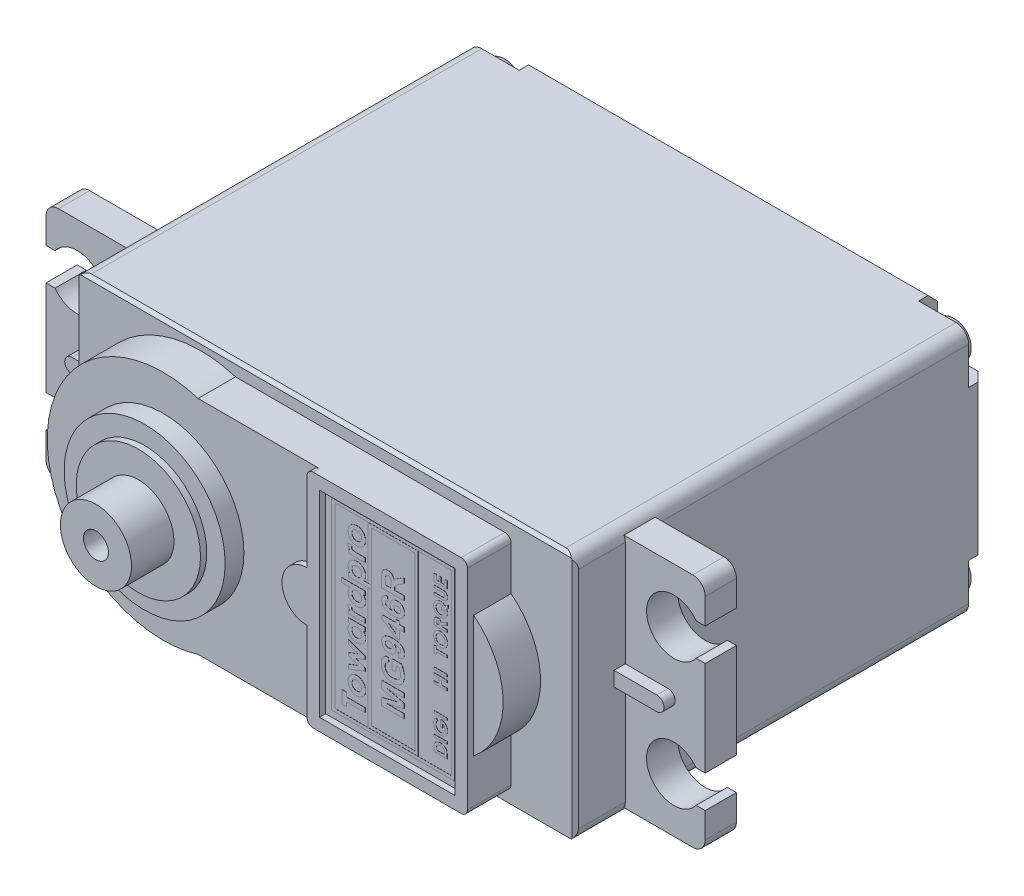
SolidWorks part; units mm, degrees
ref_plane "Front Plane" through (0, 0, 0) normal (0, 0, 1) x (1, 0, 0)
ref_plane "Top Plane" through (0, 0, 0) normal (0, 1, 0) x (1, 0, 0)
ref_plane "Right Plane" through (0, 0, 0) normal (1, 0, 0) x (0, 0, -1)
ref_plane "Plane1" through (0, -10, 0) normal (0, -1, 0) x (1, 0, 0)
sketch "Sketch1" plane through (0, -10, 0) normal (0, -1, 0) x (1, 0, 0)
  line L0 (-20, 16.5) -> (-20, -16.5)
  line L1 (-20, -16.5) -> (20, -16.5)
  line L2 (20, -16.5) -> (20, 16.5)
  line L3 (20, 16.5) -> (-20, 16.5)
extrude "Boss-Extrude1" add sketch "Sketch1" against normal blind 20
sketch "Sketch2" plane through (0, 0, 16.5) normal (0, 0, 1) x (1, 0, 0)
  line L0 (14.8541, 8.875) -> (14.8541, -8.875)
  line L1 (14.8541, -8.875) -> (-7.2207, -8.875)
  line L2 (-7.2207, 8.875) -> (14.8541, 8.875)
  arc A0 (-7.2207, -8.875) -> (-7.2207, 8.875) centre (-10, 0) cw
extrude "Boss-Extrude2" add sketch "Sketch2" along normal blind 3
sketch "Sketch3" plane through (0, 0, 19.5) normal (0, 0, 1) x (1, 0, 0)
  line L0 (2.0041, 8.875) -> (14.8541, 8.875)
  line L1 (14.8541, 8.875) -> (14.8541, -8.875)
  line L2 (14.8541, -8.875) -> (2.0041, -8.875)
  line L3 (2.0041, -8.875) -> (2.0041, 8.875)
extrude "Boss-Extrude3" add sketch "Sketch3" along normal blind 0.5
sketch "Sketch4" plane through (0, 0, 19.5) normal (0, 0, 1) x (1, 0, 0)
  line L0 (2.0041, 2) -> (2.0041, -2)
  arc A0 (2.0041, -2) -> (2.0041, 2) centre (2.0041, 0) cw
extrude "Boss-Extrude4" add sketch "Sketch4" along normal blind 0.5
sketch "Sketch5" plane through (-20, 0, 0) normal (-1, 0, 0) x (0, 0, 1)
  line L0 (10, 9.45) -> (12.5, 9.45)
  line L1 (12.5, 9.45) -> (12.5, -9.45)
  line L2 (12.5, -9.45) -> (10, -9.45)
  line L3 (10, -9.45) -> (10, 9.45)
extrude "Boss-Extrude5" add sketch "Sketch5" along normal blind 6.4
sketch "Sketch6" plane through (0, 0, 10) normal (0, 0, -1) x (-1, 0, 0)
  line L0 (26.4, 6.4) -> (25.6748, 6.4)
  line L1 (25.6748, 3.8) -> (26.4, 3.8)
  line L2 (26.4, 3.8) -> (26.4, 6.4)
  arc A0 (25.6748, 6.4) -> (25.6748, 3.8) centre (23.9, 5.1) cw
extrude "Cut-Extrude1" cut sketch "Sketch6" against normal through all
sketch "Sketch7" plane through (0, 0, 10) normal (0, 0, -1) x (-1, 0, 0)
  line L0 (26.4, -3.8) -> (25.6748, -3.8)
  line L1 (25.6748, -6.4) -> (26.4, -6.4)
  line L2 (26.4, -6.4) -> (26.4, -3.8)
  arc A0 (25.6748, -3.8) -> (25.6748, -6.4) centre (23.9, -5.1) cw
extrude "Cut-Extrude2" cut sketch "Sketch7" against normal through all
sketch "Sketch8" plane through (20, 0, 0) normal (1, 0, 0) x (0, 0, -1)
  line L0 (-10, -9.45) -> (-12.5, -9.45)
  line L1 (-12.5, -9.45) -> (-12.5, 9.45)
  line L2 (-12.5, 9.45) -> (-10, 9.45)
  line L3 (-10, 9.45) -> (-10, -9.45)
extrude "Boss-Extrude6" add sketch "Sketch8" along normal blind 6.4
sketch "Sketch9" plane through (0, 0, 12.5) normal (0, 0, 1) x (1, 0, 0)
  line L0 (26.4, 3.8) -> (26.4, 6.4)
  line L1 (26.4, 6.4) -> (25.6748, 6.4)
  line L2 (25.6748, 3.8) -> (26.4, 3.8)
  arc A0 (25.6748, 6.4) -> (25.6748, 3.8) centre (23.9, 5.1) cw
extrude "Cut-Extrude3" cut sketch "Sketch9" against normal through all
sketch "Sketch10" plane through (0, 0, 12.5) normal (0, 0, 1) x (1, 0, 0)
  line L0 (26.4, -6.4) -> (26.4, -3.8)
  line L1 (26.4, -3.8) -> (25.6748, -3.8)
  line L2 (25.6748, -6.4) -> (26.4, -6.4)
  arc A0 (25.6748, -3.8) -> (25.6748, -6.4) centre (23.9, -5.1) cw
extrude "Cut-Extrude4" cut sketch "Sketch10" against normal through all
sketch "Sketch11" plane through (0, 0, 12.5) normal (0, 0, 1) x (1, 0, 0)
  line L0 (-23.42, 0.58) -> (-20, 0.58)
  line L1 (-20, 0.58) -> (-20, -0.58)
  line L2 (-20, -0.58) -> (-23.42, -0.58)
  arc A0 (-23.42, -0.58) -> (-23.42, 0.58) centre (-23.42, 0) cw
extrude "Boss-Extrude7" add sketch "Sketch11" along normal blind 0.9
sketch "Sketch12" plane through (0, 10, 0) normal (0, 1, 0) x (-1, 0, 0)
  line L0 (-16, -16.5) -> (-16, -15)
  line L1 (-16, -15) -> (-20, -15)
  line L2 (-20, -15) -> (-20, -16.5)
  line L3 (-20, -16.5) -> (-16, -16.5)
extrude "Cut-Extrude5" cut sketch "Sketch12" against normal blind 4
sketch "Sketch13" plane through (-20, 0, 0) normal (-1, 0, 0) x (0, 0, 1)
  line L0 (-16.5, 6) -> (-15, 6)
  line L1 (-15, 6) -> (-15, 10)
  line L2 (-15, 10) -> (-16.5, 10)
  line L3 (-16.5, 10) -> (-16.5, 6)
extrude "Cut-Extrude6" cut sketch "Sketch13" against normal blind 4
sketch "Sketch14" plane through (-20, 0, 0) normal (-1, 0, 0) x (0, 0, 1)
  line L0 (-16.5, -10) -> (-15, -10)
  line L1 (-15, -10) -> (-15, -6)
  line L2 (-15, -6) -> (-16.5, -6)
  line L3 (-16.5, -6) -> (-16.5, -10)
extrude "Cut-Extrude7" cut sketch "Sketch14" against normal blind 4
sketch "Sketch15" plane through (0, -10, 0) normal (0, -1, 0) x (1, 0, 0)
  line L0 (20, -16.5) -> (20, -15)
  line L1 (20, -15) -> (16, -15)
  line L2 (16, -15) -> (16, -16.5)
  line L3 (16, -16.5) -> (20, -16.5)
extrude "Cut-Extrude8" cut sketch "Sketch15" against normal blind 4
sketch "Sketch16" plane through (0, 0, 12.5) normal (0, 0, 1) x (1, 0, 0)
  line L0 (23.42, -0.58) -> (20, -0.58)
  line L1 (20, -0.58) -> (20, 0.58)
  line L2 (20, 0.58) -> (23.42, 0.58)
  arc A0 (23.42, 0.58) -> (23.42, -0.58) centre (23.42, 0) cw
extrude "Boss-Extrude8" add sketch "Sketch16" along normal blind 0.9
sketch "Sketch17" plane through (0, 0, 16.5) normal (0, 0, 1) x (1, 0, 0)
  line L0 (14.8541, -4.875) -> (14.8541, 4.875)
  arc A0 (14.8541, 4.875) -> (14.8541, -4.875) centre (11, 0) cw
extrude "Boss-Extrude9" add sketch "Sketch17" along normal blind 3
sketch "Sketch18" plane through (0, 0, 20) normal (0, 0, 1) x (1, 0, 0)
  line L0 (13.8541, 7.875) -> (3.0041, 7.875)
  line L1 (3.0041, 7.875) -> (3.0041, -7.875)
  line L2 (3.0041, -7.875) -> (13.8541, -7.875)
  line L3 (13.8541, -7.875) -> (13.8541, 7.875)
extrude "Cut-Extrude9" cut sketch "Sketch18" against normal blind 0.5
sketch "Sketch19" plane through (0, 0, 0) normal (0, 1, 0) x (1, 0, 0)
  line L0 (-3.55, -19.5) -> (-10, -19.5)
  line L1 (-10, -19.5) -> (-10, -24.9)
  line L2 (-10, -24.9) -> (-7.15, -24.9)
  line L3 (-7.15, -24.9) -> (-7.15, -21.5)
  line L4 (-7.15, -21.5) -> (-5.025, -21.5)
  line L5 (-5.025, -21.5) -> (-5.025, -21)
  line L6 (-5.025, -21) -> (-3.55, -21)
  line L7 (-3.55, -21) -> (-3.55, -19.5)
  line L8 (-10, -19.5) -> (-10, -24.9) construction
revolve "Revolve1" add sketch "Sketch19" angle 360 about L8 reverse direction yes
ref_plane "Plane2" through (0, -5.1, 0) normal (0, -1, 0) x (1, 0, 0)
sketch "Sketch20" plane through (0, -5.1, 0) normal (0, -1, 0) x (1, 0, 0)
  line L0 (26.1, 12.5) -> (23.9, 12.5)
  line L1 (23.9, 12.5) -> (23.9, 10)
  line L2 (23.9, 10) -> (26.1, 10)
  line L3 (26.1, 10) -> (26.1, 12.5)
  line L4 (23.9, 12.5) -> (23.9, 10) construction
revolve "Cut-Revolve1" cut sketch "Sketch20" angle 360 about L4 reverse direction yes
ref_plane "Plane3" through (0, 5.1, 0) normal (0, -1, 0) x (1, 0, 0)
sketch "Sketch21" plane through (0, 5.1, 0) normal (0, -1, 0) x (1, 0, 0)
  line L0 (26.1, 12.5) -> (23.9, 12.5)
  line L1 (23.9, 12.5) -> (23.9, 10)
  line L2 (23.9, 10) -> (26.1, 10)
  line L3 (26.1, 10) -> (26.1, 12.5)
  line L4 (23.9, 12.5) -> (23.9, 10) construction
revolve "Cut-Revolve2" cut sketch "Sketch21" angle 360 about L4 reverse direction yes
sketch "Sketch22" plane through (0, 5.1, 0) normal (0, -1, 0) x (1, 0, 0)
  line L0 (-21.7, 12.5) -> (-23.9, 12.5)
  line L1 (-23.9, 12.5) -> (-23.9, 10)
  line L2 (-23.9, 10) -> (-21.7, 10)
  line L3 (-21.7, 10) -> (-21.7, 12.5)
  line L4 (-23.9, 12.5) -> (-23.9, 10) construction
revolve "Cut-Revolve3" cut sketch "Sketch22" angle 360 about L4 reverse direction yes
sketch "Sketch23" plane through (0, -5.1, 0) normal (0, -1, 0) x (1, 0, 0)
  line L0 (-21.7, 12.5) -> (-23.9, 12.5)
  line L1 (-23.9, 12.5) -> (-23.9, 10)
  line L2 (-23.9, 10) -> (-21.7, 10)
  line L3 (-21.7, 10) -> (-21.7, 12.5)
  line L4 (-23.9, 12.5) -> (-23.9, 10) construction
revolve "Cut-Revolve4" cut sketch "Sketch23" angle 360 about L4 reverse direction yes
hole_wizard "Ø2.0 (2) Diameter Hole1" positions "Sketch25" profile "Sketch24" hole size "Ø2.0" standard "ANSI Metric"
sketch "Sketch25" plane through (0, 0, 24.9) normal (0, 0, 1) x (1, 0, 0)
  point P0 (-10, 0)
sketch "Sketch24" plane through (-10, 0, 24.9) normal (1, 0, 0) x (0, -1, 0)
  line L0 (0, 0) -> (0, 3.4)
  line L1 (0, 3.4) -> (1, 3.4)
  line L2 (1, 3.4) -> (1, 0)
  line L5 (1, 0) -> (0, 0)
  line L10 (0, 3.4) -> (-1, 3.4) construction
  line L11 (0, -6.35) -> (0, 107.95) construction
  dimension "Hole Dia." = 2
  dimension "Hole Depth" = 3.4
  dimension "Drill Angle" = 180
hole_wizard "Ø1.8 (1.8) Diameter Hole1" positions "Sketch27" profile "Sketch26" hole size "Ø1.8" standard "ANSI Metric"
sketch "Sketch27" plane through (0, 0, -15) normal (0, 0, -1) x (-1, 0, 0)
  point P0 (-18, 8)
  point P1 (18, 8)
  point P2 (18, -8)
  point P3 (-18, -8)
sketch "Sketch26" plane through (18, 8, -15) normal (1, 0, 0) x (0, 1, 0)
  line L0 (0, 0) -> (0, 8.5408)
  line L1 (0, 8.5408) -> (0.9, 8)
  line L2 (0.9, 8) -> (0.9, 0)
  line L5 (0.9, 0) -> (0, 0)
  line L10 (0, 8.5408) -> (-0.9, 8) construction
  line L11 (0, -6.35) -> (0, 107.95) construction
  dimension "Hole Dia." = 1.8
  dimension "Hole Depth" = 8
  dimension "Drill Angle" = 118
chamfer "Chamfer1" distance 0.25 angle 45 4 edges at (20, 0, 16.5) (0, 10, 16.5) (-20, 0, 16.5) (0, -10, 16.5)
chamfer "Chamfer2" distance 0.75 angle 45 4 edges at (0, 10, -16.5) (20, 0, -16.5) (0, -10, -16.5) (-20, 0, -16.5)
fillet "Fillet1" radius 0.5 4 edges at (14.8541, -8.875, 18.25) (14.8541, 8.875, 18.25) tangent propagation no
fillet "Fillet2" radius 1 8 edges at (20, 10, 0.625) (20, -10, 0.625) (26.4, 9.45, 11.25) (-20, -10, 0.625) (26.4, -9.45, 11.25) (-26.4, -9.45, 11.25) (-26.4, 9.45, 11.25) (-20, 10, 0.625) tangent propagation no
fillet "Fillet3" radius 2 4 edges at (-16, 6, -15.75) (16, 6, -15.75) (-16, -6, -15.75) (16, -6, -15.75) tangent propagation no
sketch "Sketch28" plane through (0, 0, 19.5) normal (0, 0, 1) x (1, 0, 0)
  line L1 (3.0041, -7.875) -> (13.8541, -7.875)
  line L2 (3.0041, -7.875) -> (3.0041, 7.875)
  line L3 (3.0041, 7.875) -> (13.8541, 7.875)
  line L4 (13.8541, -7.875) -> (13.8541, 7.875)
extrude "Boss-Extrude10" add sketch "Sketch28" along normal blind 0.01
sketch "Sketch29" plane through (0, 0, 19.51) normal (0, 0, 1) x (1, 0, 0)
  line L0 (6.8665, -7.875) -> (6.8665, -7.375) construction
  line L1 (3.0041, -7.875) -> (13.8541, -7.875) construction
  line L2 (3.0041, 1.859) -> (3.5041, 1.859) construction
  line L3 (3.0041, 7.875) -> (3.0041, -7.875) construction
  line L4 (10.2846, 7.875) -> (10.2846, 7.375) construction
  line L5 (13.8541, 7.875) -> (3.0041, 7.875) construction
  line L6 (13.8541, -1.5785) -> (13.3541, -1.5785) construction
  line L7 (13.8541, -7.875) -> (13.8541, 7.875) construction
  line L8 (3.7541, 7.125) -> (13.1041, 7.125)
  line L9 (3.5041, -7.375) -> (13.3541, -7.375)
  line L10 (3.5041, -7.375) -> (3.5041, 7.375)
  line L11 (3.5041, 7.375) -> (13.3541, 7.375)
  line L12 (13.3541, -7.375) -> (13.3541, 7.375)
  line L13 (13.1041, -7.125) -> (13.1041, 7.125)
  line L14 (3.7541, -7.125) -> (13.1041, -7.125)
  line L15 (3.7541, -7.125) -> (3.7541, 7.125)
  line L16 (8.4291, -7.125) -> (8.4291, -7.115) construction
  line L17 (8.4291, -7.115) -> (6.4291, -7.115) construction
  line L18 (8.4291, -4.0034) -> (10.4291, -4.0034) construction
  line L19 (9.3693, 7.125) -> (9.3693, 7.115) construction
  line L20 (10.4291, -4.0034) -> (10.4291, 6.8709) construction
  line L21 (6.6791, -6.865) -> (6.6791, 6.865)
  line L22 (6.4291, -7.115) -> (10.4291, -7.115)
  line L23 (6.4291, -7.115) -> (6.4291, 7.115)
  line L24 (6.4291, 7.115) -> (10.4291, 7.115)
  line L25 (10.4291, -7.115) -> (10.4291, 7.115)
  line L26 (6.6791, 6.865) -> (10.1791, 6.865)
  line L27 (10.1791, -6.865) -> (10.1791, 6.865)
  line L28 (6.6791, -6.865) -> (10.1791, -6.865)
  dimension "D1" = 0.25
  dimension "D2" = 0.25
extrude "Boss-Extrude11" add sketch "Sketch29" along normal blind 0.01 contours L22 L25 L24 L23 L28 L21 L26 L27 | L9 L12 L11 L10 L14 L15 L8 L13 region at (3.6815, 0, 19.51) region at (6.5769, 0, 19.51)
sketch "Sketch30" plane through (0, 0, 19.51) normal (0, 0, 1) x (1, 0, 0)
  line L0 (9.3092, -6.0531) -> (9.3092, 5.5838) construction
  line L1 (12.7516, 6.631) -> (12.7516, -6.6636) construction
  line L2 (6.1944, -6.6636) -> (6.1944, 6.8512) construction
  text T0 "<b>Towardpro</b>" font "Century Gothic" height in points 7
  text T1 "<b>DIGI    HI  TORQUE</b>" font "Century Gothic" height in points 4
  text T2 "MG946R" font "Arial" height in points 7
extrude "Boss-Extrude12" add sketch "Sketch30" along normal blind 0.015
sketch "Sketch31" plane through (0, 0, -15) normal (0, 0, -1) x (-1, 0, 0)
  circle A0 centre (18, 8) radius 1.5
  circle A1 centre (18, -8) radius 1.5
  circle A2 centre (-18, 8) radius 1.5
  circle A3 centre (-18, -8) radius 1.5
extrude "Boss-Extrude13" add sketch "Sketch31" along normal blind 1
fillet "Fillet5" radius 0.5 4 edges at (-19.5, 8, -16) (-19.5, -8, -16) (16.5, -8, -16) (16.5, 8, -16)
sketch "Sketch32" plane through (0, 0, -16) normal (0, 0, -1) x (-1, 0, 0)
  line L0 (19, 8) -> (19, 8.5) construction
  line L1 (17, 8) -> (17, 7.5) construction
  line L2 (18, 9) -> (17.5, 9) construction
  line L3 (18, 7) -> (18.5, 7) construction
  line L4 (19, 8.5) -> (19, 7.5)
  line L5 (19, 7.5) -> (18.5, 7.5)
  line L6 (18.5, 7.5) -> (18.5, 7)
  line L7 (18.5, 7) -> (17.5, 7)
  line L8 (17.5, 7) -> (17.5, 7.5)
  line L9 (17.5, 7.5) -> (17, 7.5)
  line L10 (17, 7.5) -> (17, 8.5)
  line L11 (17, 8.5) -> (17.5, 8.5)
  line L12 (17.5, 8.5) -> (17.5, 9)
  line L13 (17.5, 9) -> (18.5, 9)
  line L14 (18.5, 9) -> (18.5, 8.5)
  line L15 (18.5, 8.5) -> (19, 8.5)
  line L16 (19, -8) -> (19, -8.5) construction
  line L17 (17, -8) -> (17, -7.5) construction
  line L18 (18, -7) -> (17.5, -7) construction
  line L19 (18, -9) -> (18.5, -9) construction
  line L20 (-17, -8) -> (-17, -7.5) construction
  line L21 (-18, -7) -> (-18.5, -7) construction
  line L22 (-18, -9) -> (-17.5, -9) construction
  line L23 (-19, -8) -> (-19, -8.5) construction
  line L24 (-17, -7.5) -> (-17, -8.5)
  line L25 (-17, -8.5) -> (-17.5, -8.5)
  line L26 (-17.5, -8.5) -> (-17.5, -9)
  line L27 (-17.5, -9) -> (-18.5, -9)
  line L28 (-18.5, -9) -> (-18.5, -8.5)
  line L29 (-18.5, -8.5) -> (-19, -8.5)
  line L30 (-19, -8.5) -> (-19, -7.5)
  line L31 (-19, -7.5) -> (-18.5, -7.5)
  line L32 (-18.5, -7.5) -> (-18.5, -7)
  line L33 (-18.5, -7) -> (-17.5, -7)
  line L34 (-17.5, -7) -> (-17.5, -7.5)
  line L35 (-17.5, -7.5) -> (-17, -7.5)
  line L36 (19, -7.5) -> (19, -8.5)
  line L37 (19, -8.5) -> (18.5, -8.5)
  line L38 (18.5, -8.5) -> (18.5, -9)
  line L39 (18.5, -9) -> (17.5, -9)
  line L40 (17.5, -9) -> (17.5, -8.5)
  line L41 (17.5, -8.5) -> (17, -8.5)
  line L42 (17, -8.5) -> (17, -7.5)
  line L43 (17, -7.5) -> (17.5, -7.5)
  line L44 (17.5, -7.5) -> (17.5, -7)
  line L45 (17.5, -7) -> (18.5, -7)
  line L46 (18.5, -7) -> (18.5, -7.5)
  line L47 (18.5, -7.5) -> (19, -7.5)
  line L48 (-17, 8.5) -> (-17, 7.5)
  line L49 (-17, 7.5) -> (-17.5, 7.5)
  line L50 (-17.5, 7.5) -> (-17.5, 7)
  line L51 (-17.5, 7) -> (-18.5, 7)
  line L52 (-18.5, 7) -> (-18.5, 7.5)
  line L53 (-18.5, 7.5) -> (-19, 7.5)
  line L54 (-19, 7.5) -> (-19, 8.5)
  line L55 (-19, 8.5) -> (-18.5, 8.5)
  line L56 (-18.5, 8.5) -> (-18.5, 9)
  line L57 (-18.5, 9) -> (-17.5, 9)
  line L58 (-17.5, 9) -> (-17.5, 8.5)
  line L59 (-17.5, 8.5) -> (-17, 8.5)
  circle A0 centre (18, 8) radius 1 construction
  circle A1 centre (18, -8) radius 1 construction
  circle A2 centre (-18, -8) radius 1 construction
extrude "Cut-Extrude10" cut sketch "Sketch32" against normal blind 0.7
chamfer "Chamfer3" distance 0.6 angle 35 48 edges at (17, 8, -15.3) (17.25, 7.5, -15.3) (17.5, 7.25, -15.3) (18, 7, -15.3) (18.5, 7.25, -15.3) (18.75, 7.5, -15.3) (19, 8, -15.3) (18.75, 8.5, -15.3) (18.5, 8.75, -15.3) (18, 9, -15.3) (17.5, 8.75, -15.3) (17.25, 8.5, -15.3) (17, -8, -15.3) (17.25, -8.5, -15.3) (17.5, -8.75, -15.3) (18, -9, -15.3) (18.5, -8.75, -15.3) (18.75, -8.5, -15.3) (19, -8, -15.3) (18.75, -7.5, -15.3) (18.5, -7.25, -15.3) (18, -7, -15.3) (17.5, -7.25, -15.3) (17.25, -7.5, -15.3) (-18.5, -8.75, -15.3) (-18, -9, -15.3) (-17.5, -8.75, -15.3) (-17.25, -8.5, -15.3) (-17, -8, -15.3) (-17.25, -7.5, -15.3) (-17.5, -7.25, -15.3) (-18, -7, -15.3) (-18.5, -7.25, -15.3) (-18.75, -7.5, -15.3) (-19, -8, -15.3) (-18.75, -8.5, -15.3) (-19, 8, -15.3) (-18.75, 7.5, -15.3) (-18.5, 7.25, -15.3) (-18, 7, -15.3) (-17.5, 7.25, -15.3) (-17.25, 7.5, -15.3) (-17, 8, -15.3) (-17.25, 8.5, -15.3) (-17.5, 8.75, -15.3) (-18, 9, -15.3) (-18.5, 8.75, -15.3) (-18.75, 8.5, -15.3) first distance on face at (17, 8.155, -15.4045) first distance on face at (17.2402, 7.5, -15.7186) first distance on face at (17.5, 7.2134, -15.7158) first distance on face at (17.845, 7, -15.4045) first distance on face at (18.5, 7.2402, -15.7186) first distance on face at (18.7866, 7.5, -15.7158) first distance on face at (19, 7.845, -15.4045) first distance on face at (18.7598, 8.5, -15.7186) first distance on face at (18.5, 8.7866, -15.7158) first distance on face at (18.155, 9, -15.4045) first distance on face at (17.5, 8.7598, -15.7186) first distance on face at (17.2134, 8.5, -15.7158) first distance on face at (17, -7.845, -15.4045) first distance on face at (17.2402, -8.5, -15.7186) first distance on face at (17.5, -8.7866, -15.7158) first distance on face at (17.845, -9, -15.4045) first distance on face at (18.5, -8.7598, -15.7186) first distance on face at (18.7866, -8.5, -15.7158) first distance on face at (19, -8.155, -15.4045) first distance on face at (18.7598, -7.5, -15.7186) first distance on face at (18.5, -7.2134, -15.7158) first distance on face at (18.155, -7, -15.4045) first distance on face at (17.5, -7.2402, -15.7186) first distance on face at (17.2134, -7.5, -15.7158) first distance on face at (-18.5, -8.7866, -15.7158) first distance on face at (-18.155, -9, -15.4045) first distance on face at (-17.5, -8.7598, -15.7186) first distance on face at (-17.2134, -8.5, -15.7158) first distance on face at (-17, -8.155, -15.4045) first distance on face at (-17.2402, -7.5, -15.7186) first distance on face at (-17.5, -7.2134, -15.7158) first distance on face at (-17.845, -7, -15.4045) first distance on face at (-18.5, -7.2402, -15.7186) first distance on face at (-18.7866, -7.5, -15.7158) first distance on face at (-19, -7.845, -15.4045) first distance on face at (-18.7598, -8.5, -15.7186) first distance on face at (-19, 8.155, -15.4045) first distance on face at (-18.7598, 7.5, -15.7186) first distance on face at (-18.5, 7.2134, -15.7158) first distance on face at (-18.155, 7, -15.4045) first distance on face at (-17.5, 7.2402, -15.7186) first distance on face at (-17.2134, 7.5, -15.7158) first distance on face at (-17, 7.845, -15.4045) first distance on face at (-17.2402, 8.5, -15.7186) first distance on face at (-17.5, 8.7866, -15.7158) first distance on face at (-17.845, 9, -15.4045) first distance on face at (-18.5, 8.7598, -15.7186) first distance on face at (-18.7866, 8.5, -15.7158)
fillet "Fillet8" radius 0.1 48 edges at (17.9201, 7.6701, -15.3) (18, 7.4201, -15.3) (18.0799, 7.6701, -15.3) (18.3299, 7.9201, -15.3) (18.5799, 8, -15.3) (18.3299, 8.0799, -15.3) (18.0799, 8.3299, -15.3) (18, 8.5799, -15.3) (17.9201, 8.3299, -15.3) (17.6701, 8.0799, -15.3) (17.4201, 8, -15.3) (17.6701, 7.9201, -15.3) (17.9201, -8.3299, -15.3) (18, -8.5799, -15.3) (18.0799, -8.3299, -15.3) (18.3299, -8.0799, -15.3) (18.5799, -8, -15.3) (18.3299, -7.9201, -15.3) (18.0799, -7.6701, -15.3) (18, -7.4201, -15.3) (17.9201, -7.6701, -15.3) (17.6701, -7.9201, -15.3) (17.4201, -8, -15.3) (17.6701, -8.0799, -15.3) (-17.9201, -8.3299, -15.3) (-17.6701, -8.0799, -15.3) (-17.4201, -8, -15.3) (-17.6701, -7.9201, -15.3) (-17.9201, -7.6701, -15.3) (-18, -7.4201, -15.3) (-18.0799, -7.6701, -15.3) (-18.3299, -7.9201, -15.3) (-18.5799, -8, -15.3) (-18.3299, -8.0799, -15.3) (-18.0799, -8.3299, -15.3) (-18, -8.5799, -15.3) (-18.0799, 7.6701, -15.3) (-18, 7.4201, -15.3) (-17.9201, 7.6701, -15.3) (-17.6701, 7.9201, -15.3) (-17.4201, 8, -15.3) (-17.6701, 8.0799, -15.3) (-17.9201, 8.3299, -15.3) (-18, 8.5799, -15.3) (-18.0799, 8.3299, -15.3) (-18.3299, 8.0799, -15.3) (-18.5799, 8, -15.3) (-18.3299, 7.9201, -15.3)
